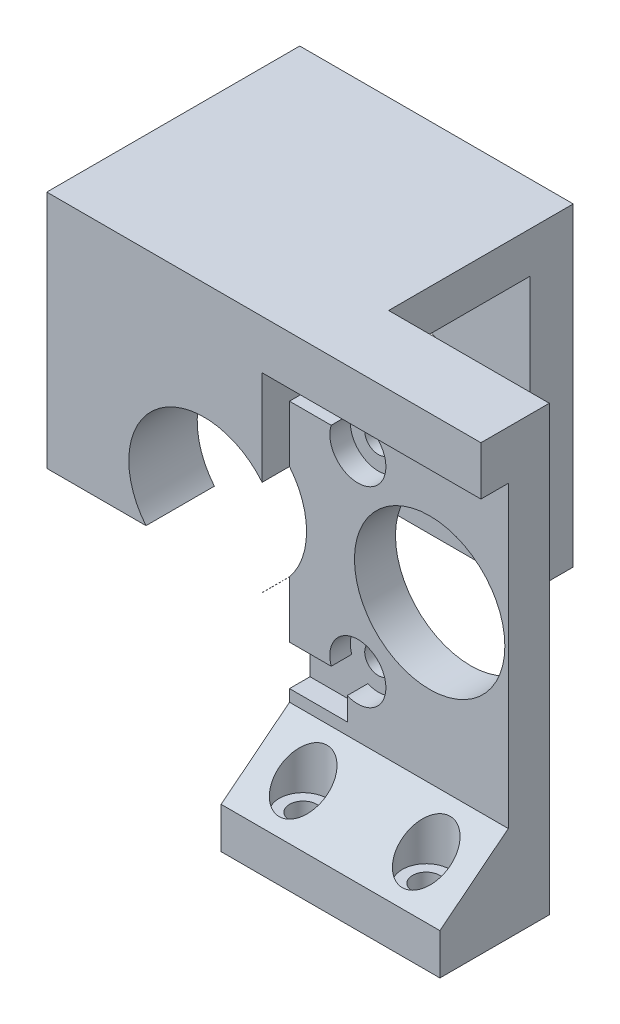
SolidWorks part; units mm, degrees
material "ABS"
ref_plane "Front Plane" through (0, 0, 0) normal (0, 0, 1) x (1, 0, 0)
ref_plane "Top Plane" through (0, 0, 0) normal (0, 1, 0) x (1, 0, 0)
ref_plane "Right Plane" through (0, 0, 0) normal (1, 0, 0) x (0, 0, -1)
sketch "Sketch1" plane through (0, 0, 0) normal (0, 0, 1) x (1, 0, 0)
  line L1 (-76.1871, 64.9281) -> (16.8129, 64.9281)
  line L2 (-76.1871, 64.9281) -> (-76.1871, -35.0719)
  line L3 (-76.1871, -35.0719) -> (16.8129, -35.0719)
  line L4 (16.8129, 64.9281) -> (16.8129, -35.0719)
  dimension "D1" = 93
  dimension "D2" = 100
extrude "Boss-Extrude2" add sketch "Sketch1" along normal blind 10 contours L1 L4 L3 L2
sketch "Sketch3" plane through (0, 0, 0) normal (0, 0, -1) x (-1, 0, 0)
  line L0 (76.1871, -35.0719) -> (-16.8129, -35.0719) construction
  line L1 (-16.8129, 64.9281) -> (-6.8129, 64.9281)
  line L2 (-16.8129, 64.9281) -> (-16.8129, -35.0719)
  line L3 (-16.8129, -35.0719) -> (-6.8129, -35.0719)
  line L4 (-6.8129, 64.9281) -> (-6.8129, -35.0719)
  line L5 (-16.8129, 64.9281) -> (-16.8129, -35.0719) construction
  dimension "D1" = 0
  dimension "D2" = 0
  dimension "D3" = 10
  dimension "D4" = 100
sketch "Sketch4" plane through (16.8129, 0, 0) normal (1, 0, 0) x (0, 0, -1)
  line L0 (-10, 64.9281) -> (-10, -35.0719) construction
  line L1 (-10, -5.0719) -> (0.01, -5.0719)
  line L2 (-10, -5.0719) -> (-10, -20.0719)
  line L3 (-10, -20.0719) -> (0.01, -20.0719)
  line L4 (0.01, -5.0719) -> (0.01, -20.0719)
  line L6 (-10, -35.0719) -> (0, -35.0719) construction
  dimension "D1" = 15
  dimension "D2" = 15
extrude "Boss-Extrude4" add sketch "Sketch4" along normal blind 24
sketch "Sketch5" plane through (0, -5.0719, 0) normal (0, 1, 0) x (1, 0, 0)
  line L0 (40.8129, -10) -> (16.8129, -10) construction
  line L2 (16.8129, 0) -> (16.8129, -10) construction
  circle A0 centre (26.8129, -5) radius 2
  dimension "D2" = 4
  dimension "D3" = 10
  dimension "D1" = 5
extrude "Cut-Extrude1" cut sketch "Sketch5" against normal blind 50
sketch "Sketch6" plane through (0, 0, 10) normal (0, 0, -1) x (-1, 0, 0)
  line L2 (76.1871, -35.0719) -> (-16.8129, -35.0719) construction
  line L3 (-16.8129, 64.9281) -> (-16.8129, -35.0719) construction
  circle A0 centre (-1.8129, -24.5719) radius 7.5
  dimension "D1" = 15
  dimension "D2" = 10.5
  dimension "D3" = 15
sketch "Sketch7" plane through (0, 0, 0) normal (0, 0, -1) x (-1, 0, 0)
  circle A0 centre (24.1871, 36.9281) radius 11
  circle A1 centre (24.1871, 36.9281) radius 9.3 construction
  dimension "D1" = 22
extrude "Cut-Extrude3" cut sketch "Sketch7" against normal blind 50
sketch "Sketch14" plane through (0, 0, 10) normal (0, 0, 1) x (1, 0, 0)
  line L0 (16.8129, 64.9281) -> (16.8129, -5.0719) construction
  line L1 (-44.6871, 15.7891) -> (16.8129, 15.7891)
  line L2 (-44.6871, 15.7891) -> (-44.6871, 57.7891)
  line L3 (-44.6871, 57.7891) -> (16.8129, 57.7891)
  line L4 (16.8129, 15.7891) -> (16.8129, 57.7891)
  dimension "D1" = 42
  dimension "D3" = 61.5
extrude "Cut-Extrude8" cut sketch "Sketch14" against normal blind 4
sketch "Sketch15" plane through (0, 0, 0) normal (0, 0, -1) x (-1, 0, 0)
  circle A0 centre (24.1871, 36.9281) radius 10
  circle A1 centre (24.1871, 36.9281) radius 11 construction
  dimension "D1" = 20
  dimension "D2" = 0
sketch "Sketch16" plane through (0, 0, 10) normal (0, 0, 1) x (1, 0, 0)
  line L0 (-43.6871, 56.9281) -> (14.3129, 56.9281) construction
  line L1 (-44.1871, 57.3281) -> (16.8129, 57.3281)
  line L2 (-44.1871, 57.3281) -> (-44.1871, 64.9281)
  line L3 (-44.1871, 64.9281) -> (16.8129, 64.9281)
  line L4 (16.8129, 57.3281) -> (16.8129, 64.9281)
  dimension "D1" = 0.4
sketch "Sketch17" plane through (0, 0, 10) normal (0, 0, 1) x (1, 0, 0)
  line L0 (16.8129, 15.7891) -> (16.8129, -5.0719) construction
  line L1 (-44.1871, 16.7281) -> (16.8129, 16.7281)
  line L2 (-44.1871, 16.7281) -> (-44.1871, -20.0719)
  line L3 (-44.1871, -20.0719) -> (16.8129, -20.0719)
  line L4 (16.8129, 16.7281) -> (16.8129, -20.0719)
  line L5 (-43.6871, 16.9281) -> (14.3129, 16.9281) construction
  line L6 (40.8129, -20.0719) -> (16.8129, -20.0719) construction
  line L9 (16.8129, -20.0719) -> (40.8129, -20.0719)
  line L10 (16.8129, -20.0719) -> (16.8129, -5.0719)
  line L11 (16.8129, -5.0719) -> (40.8129, -5.0719)
  line L12 (40.8129, -20.0719) -> (40.8129, -5.0719)
  line L13 (16.8129, -20.0719) -> (40.8129, -5.0719) construction
  line L14 (16.8129, -5.0719) -> (40.8129, -20.0719) construction
  point P16 (28.8129, -12.5719)
  dimension "D1" = 0.2
  dimension "D2" = 0
sketch "Sketch19" plane through (0, 0, 0) normal (0, 0, -1) x (-1, 0, 0)
  line L1 (-16.8129, 64.9281) -> (-16.8129, -35.0719) construction
  circle A0 centre (53.1871, 36.9281) radius 11
  circle A1 centre (24.1871, 36.9281) radius 10 construction
  dimension "D1" = 22
  dimension "D3" = 0
  dimension "D2" = 70
extrude "Cut-Extrude11" cut sketch "Sketch19" against normal blind 15
sketch "Sketch20" plane through (0, 0, 6) normal (0, 0, 1) x (1, 0, 0)
  circle A0 centre (-34.6871, 50.9281) radius 2
  circle A1 centre (5.3129, 50.9281) radius 2
  circle A2 centre (-34.6871, 22.9281) radius 2
  circle A3 centre (5.3129, 22.9281) radius 2
  arc A5 (-27.0471, 34.1316) -> (-27.0471, 39.7246) centre (-24.1871, 36.9281) ccw construction
  circle A6 centre (-24.1871, 36.9281) radius 11 construction
  dimension "D1" = 4
  dimension "D2" = 4
  dimension "D3" = 4
  dimension "D4" = 4
  dimension "D5" = 0
  dimension "D6" = 28
  dimension "D7" = 0
  dimension "D8" = 40
  dimension "D9" = 14
  dimension "D10" = 10.5
  dimension "D11" = 28
  dimension "D12" = 40
extrude "Cut-Extrude12" cut sketch "Sketch20" against normal blind 10
sketch "Sketch8" plane through (0, 64.9281, 0) normal (0, 1, 0) x (1, 0, 0)
  line L0 (-76.1871, -10) -> (16.8129, -10) construction
  line L5 (16.8129, 0) -> (12.3014, -10) construction
  line L6 (16.8129, -10) -> (7.8859, 0) construction
  line L8 (16.8129, -10) -> (16.8129, 0) construction
  line L9 (-76.1871, 0) -> (16.8129, 0) construction
  circle A0 centre (11.8129, -7) radius 1.4
  circle A1 centre (-13.1871, -7) radius 1.4
  point P4 (13.816, -6.6429)
  dimension "D1" = 25
  dimension "D2" = 5
  dimension "D3" = 2.8
  dimension "D4" = 7
  dimension "D5" = 7
sketch "Sketch21" plane through (0, 0, 0) normal (0, 0, -1) x (-1, 0, 0)
  line L1 (76.1871, 64.9281) -> (36.1871, 64.9281)
  line L2 (76.1871, 64.9281) -> (76.1871, 58.9281)
  line L3 (76.1871, 58.9281) -> (36.1871, 58.9281)
  line L4 (36.1871, 64.9281) -> (36.1871, 58.9281)
  dimension "D1" = 6
  dimension "D2" = 40
extrude "Boss-Extrude5" add sketch "Sketch21" along normal blind 27
sketch "Sketch22" plane through (0, 58.9281, 0) normal (0, -1, 0) x (1, 0, 0)
  line L0 (-76.1871, -27) -> (-76.1871, 0) construction
  line L1 (-36.1871, -27) -> (-76.1871, -27)
  line L2 (-36.1871, -27) -> (-36.1871, -20.7)
  line L3 (-36.1871, -20.7) -> (-76.1871, -20.7)
  line L4 (-76.1871, -27) -> (-76.1871, -20.7)
  dimension "D1" = 6.3
extrude "Boss-Extrude7" add sketch "Sketch22" along normal blind 40
sketch "Sketch23" plane through (0, 0, 10) normal (0, 0, 1) x (1, 0, 0)
  circle A0 centre (-53.1871, 36.9281) radius 8
  arc A1 (-44.6871, 43.9102) -> (-44.6871, 29.9459) centre (-53.1871, 36.9281) ccw construction
  dimension "D1" = 16
  dimension "D2" = 0
extrude "Cut-Extrude13" cut sketch "Sketch23" against normal blind 40
sketch "Sketch24" plane through (0, 0, 10) normal (0, 0, 1) x (1, 0, 0)
  line L1 (-76.1871, -35.0719) -> (42.0908, -35.0719)
  line L2 (-76.1871, -35.0719) -> (-76.1871, 6.7281)
  line L3 (-76.1871, 6.7281) -> (42.0908, 6.7281)
  line L4 (42.0908, -35.0719) -> (42.0908, 6.7281)
  dimension "D1" = 41.8
extrude "Cut-Extrude14" cut sketch "Sketch24" against normal blind 40
sketch "Sketch25" plane through (0, 0, 10) normal (0, 0, 1) x (1, 0, 0)
  line L5 (-44.6871, 29.9459) -> (-44.6871, 15.7891) construction
  line L6 (-76.1871, 6.7281) -> (-44.6871, 6.7281)
  line L7 (-76.1871, 6.7281) -> (-76.1871, 29.9281)
  line L8 (-76.1871, 29.9281) -> (-44.6871, 29.9281)
  line L9 (-44.6871, 6.7281) -> (-44.6871, 29.9281)
  arc A2 (-44.6871, 43.9102) -> (-44.6871, 29.9459) centre (-53.1871, 36.9281) ccw construction
  dimension "D1" = 7
extrude "Cut-Extrude15" cut sketch "Sketch25" against normal blind 20
sketch "Sketch26" plane through (0, 0, 6) normal (0, 0, 1) x (1, 0, 0)
  line L1 (-44.6871, 15.7891) -> (-36.2375, 15.7891)
  line L2 (-44.6871, 15.7891) -> (-44.6871, 21.6647)
  line L3 (-44.6871, 21.6647) -> (-36.2375, 21.6647)
  line L4 (-36.2375, 15.7891) -> (-36.2375, 21.6647)
  line L5 (-44.6871, 57.7891) -> (-36.2375, 57.7891)
  line L6 (-44.6871, 57.7891) -> (-44.6871, 52.1914)
  line L7 (-44.6871, 52.1914) -> (-36.2375, 52.1914)
  line L8 (-36.2375, 57.7891) -> (-36.2375, 52.1914)
  line L9 (6.8634, 52.1914) -> (14.3021, 52.1914)
  line L10 (6.8634, 52.1914) -> (6.8634, 57.7891)
  line L11 (6.8634, 57.7891) -> (14.3021, 57.7891)
  line L12 (14.3021, 52.1914) -> (14.3021, 57.7891)
  line L13 (6.8634, 20.9281) -> (14.3021, 20.9281)
  line L14 (6.8634, 20.9281) -> (6.8634, 15.7891)
  line L15 (6.8634, 15.7891) -> (14.3021, 15.7891)
  line L16 (14.3021, 20.9281) -> (14.3021, 15.7891)
  circle A0 centre (-34.6871, 22.9281) radius 2 construction
  circle A1 centre (-34.6871, 50.9281) radius 2 construction
  circle A2 centre (5.3129, 50.9281) radius 2 construction
  circle A3 centre (5.3129, 22.9281) radius 4
  circle A4 centre (5.3129, 50.9281) radius 4
  circle A5 centre (-34.6871, 50.9281) radius 4
  circle A6 centre (-34.6871, 22.9281) radius 4
  circle A7 centre (5.3129, 50.9281) radius 4
  circle A8 centre (5.3129, 22.9281) radius 4
  circle A9 centre (-34.6871, 50.9281) radius 4
  circle A10 centre (-34.6871, 22.9281) radius 4
  line M5 (-44.6871, 57.7891) -> (-44.6871, 43.9102)
  line M8 (-44.6871, 29.9281) -> (-44.6871, 15.7891)
  line M9 (-44.6871, 15.7891) -> (16.8129, 15.7891)
  line M11 (16.8129, 57.7891) -> (-44.6871, 57.7891)
  dimension "D1" = 8
  dimension "D2" = 8
  dimension "D3" = 8
  dimension "D4" = 8
extrude "Cut-Extrude18" cut sketch "Sketch26" against normal blind 3 contours A4 L9 L12 L10 M11 | A3 L14 L16 L13 M9 | A5 L8 L7 M11 M5 | A6 L3 L4 M8 M9 region at (-40.7189, 18.5733, 6) region at (10.7466, 18.2528, 6) region at (10.8466, 55.1634, 6) region at (-40.7326, 55.141, 6)
sketch "Sketch27" plane through (0, 0, 6) normal (0, 0, 1) x (1, 0, 0)
  circle A0 centre (5.3129, 50.9281) radius 4.1
  circle A1 centre (5.3129, 22.9281) radius 4
  circle A2 centre (-34.6871, 50.9281) radius 4.1
  circle A3 centre (-34.6871, 22.9281) radius 4.1
  dimension "D1" = 8.2
  dimension "D2" = 8.2
  dimension "D3" = 8
  dimension "D4" = 8.2
extrude "Cut-Extrude29" cut sketch "Sketch27" against normal blind 3
sketch "Sketch28" plane through (0, 0, 0) normal (0, 0, -1) x (-1, 0, 0)
  line L5 (-16.8129, 6.7281) -> (44.6871, 6.7281) construction
  line L6 (-16.8129, 64.9281) -> (12.6871, 64.9281)
  line L7 (-16.8129, 64.9281) -> (-16.8129, 6.7281)
  line L8 (-16.8129, 6.7281) -> (12.6871, 6.7281)
  line L9 (12.6871, 64.9281) -> (12.6871, 6.7281)
  circle A1 centre (34.6871, 22.9281) radius 2 construction
  dimension "D1" = 22
extrude "Cut-Extrude30" cut sketch "Sketch28" against normal blind 23
sketch "Sketch29" plane through (0, 15.7891, 0) normal (0, 1, 0) x (1, 0, 0)
  line L1 (-44.6871, -10) -> (-12.6871, -10)
  line L2 (-44.6871, -10) -> (-44.6871, -6)
  line L3 (-44.6871, -6) -> (-12.6871, -6)
  line L4 (-12.6871, -10) -> (-12.6871, -6)
extrude "Cut-Extrude31" cut sketch "Sketch29" against normal blind 23
sketch "Sketch31" plane through (0, 6.7281, 0) normal (0, -1, 0) x (1, 0, 0)
  line L1 (-44.6871, 6) -> (-12.6871, 6)
  line L2 (-44.6871, 6) -> (-44.6871, 0)
  line L3 (-44.6871, 0) -> (-12.6871, 0)
  line L4 (-12.6871, 6) -> (-12.6871, 0)
extrude "Boss-Extrude9" add sketch "Sketch31" along normal blind 6.6
sketch "Sketch32" plane through (0, 0, 6) normal (0, 0, 1) x (1, 0, 0)
  line L0 (-12.6871, 0.1281) -> (-12.6871, 57.7891) construction
  line L1 (-44.6871, 0.1281) -> (-12.6871, 0.1281)
  line L2 (-44.6871, 0.1281) -> (-44.6871, 6.1281)
  line L3 (-44.6871, 6.1281) -> (-12.6871, 6.1281)
  line L4 (-12.6871, 0.1281) -> (-12.6871, 6.1281)
  dimension "D1" = 6
extrude "Boss-Extrude10" add sketch "Sketch32" along normal blind 10
sketch "Sketch33" plane through (0, 6.1281, 0) normal (0, 1, 0) x (1, 0, 0)
  line L0 (-12.6871, -16) -> (-44.6871, -16) construction
  line L1 (-44.6871, -16) -> (-44.6871, -6) construction
  line L2 (-12.6871, -16) -> (-12.6871, -6) construction
  circle A0 centre (-37.6871, -11) radius 2
  circle A1 centre (-19.6871, -11) radius 2
  point P8 (-44.6871, -11)
  dimension "D1" = 4
  dimension "D2" = 4
  dimension "D3" = 0
  dimension "D4" = 5
  dimension "D5" = 7
  dimension "D6" = 7
extrude "Cut-Extrude32" cut sketch "Sketch33" against normal blind 10
sketch "Sketch34" plane through (-12.6871, 0, 0) normal (1, 0, 0) x (0, 0, -1)
  line L0 (-16, 6.1281) -> (-6, 6.1281)
  line L1 (-6, 6.1281) -> (-6, 14.0584)
  line L2 (-6, 6.1281) -> (-6, 57.7891) construction
  line L3 (-6, 14.0584) -> (-16, 6.1281)
extrude "Boss-Extrude11" add sketch "Sketch34" against normal up to vertex (32 mm away) up to point (-44.6871, 29.9281, 6)
sketch "Sketch35" plane through (0, 6.1281, 0) normal (0, -1, 0) x (1, 0, 0)
  circle A0 centre (-19.6871, 11) radius 3.5
  circle A1 centre (-37.6871, 11) radius 3.5
  dimension "D1" = 7
  dimension "D2" = 7
extrude "Cut-Extrude33" cut sketch "Sketch35" against normal blind 10
